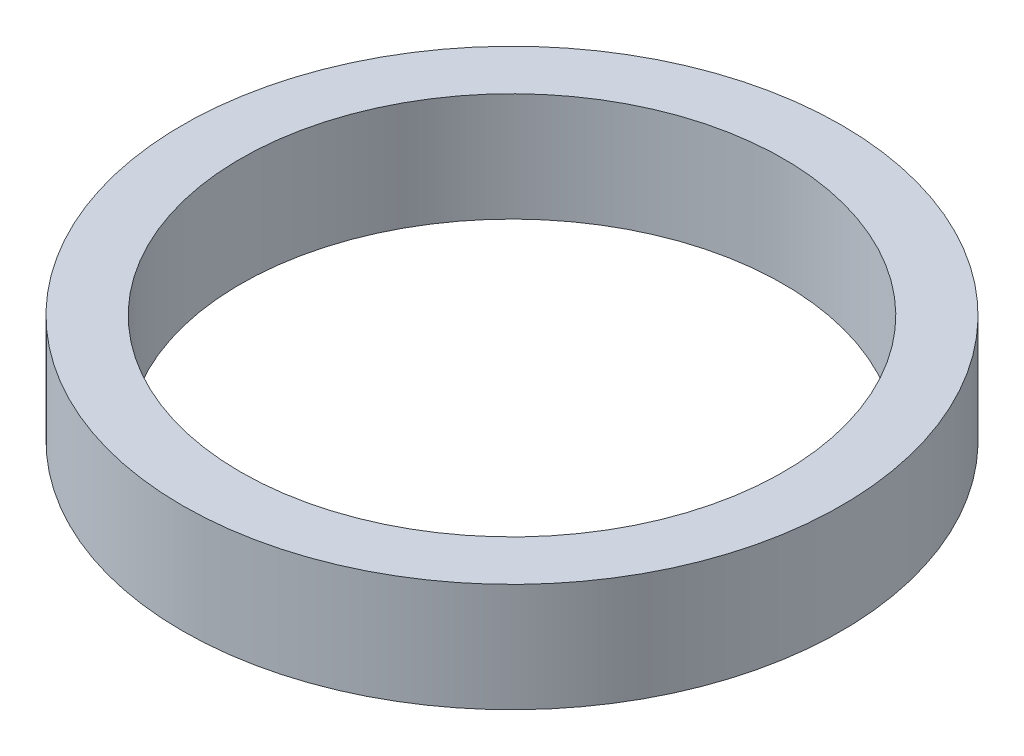
SolidWorks part; units mm, degrees
ref_plane "Front Plane" through (0, 0, 0) normal (0, 0, 1) x (1, 0, 0)
ref_plane "Top Plane" through (0, 0, 0) normal (0, 1, 0) x (1, 0, 0)
ref_plane "Right Plane" through (0, 0, 0) normal (1, 0, 0) x (0, 0, -1)
sketch "Sketch1" plane through (0, 0, 0) normal (0, 1, 0) x (1, 0, 0)
  circle A0 centre (0, 0) radius 42.5
  dimension "FLANGE_OD" = 85
extrude "Boss-Extrude1" add sketch "Sketch1" along normal blind 14
sketch "Sketch2" plane through (0, 0, 0) normal (0, 1, 0) x (1, 0, 0)
  circle A0 centre (0, 0) radius 35
  dimension "BORE_D" = 70
extrude "Cut-Extrude1" cut sketch "Sketch2" along normal through all
sketch "Sketch3" plane through (0, 14, 0) normal (0, 1, 0) x (1, 0, 0)
  circle A0 centre (0, 0) radius 19.3095 construction
  circle A1 centre (-19.3095, 0) radius 1.5
  dimension "BOLT_D" = 3
  dimension "BOLT_PCD" = 38.619
extrude "Cut-Extrude2" cut sketch "Sketch3" against normal blind 10.2924 rebuild error yes
pattern_circular "CirPattern1" count 3 over 360 rebuild error yes
